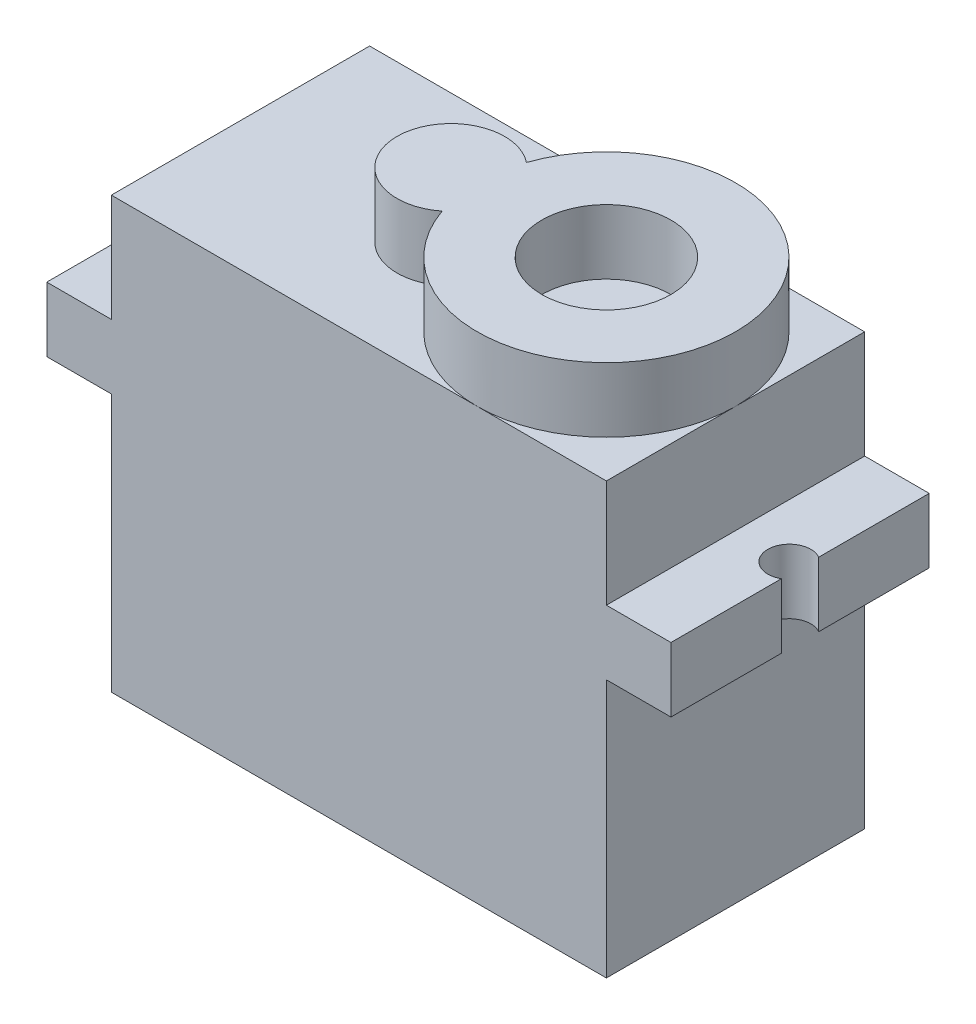
SolidWorks part; units mm, degrees
ref_plane "Front Plane" through (0, 0, 0) normal (0, 0, 1) x (1, 0, 0)
ref_plane "Top Plane" through (0, 0, 0) normal (0, 1, 0) x (1, 0, 0)
ref_plane "Right Plane" through (0, 0, 0) normal (1, 0, 0) x (0, 0, -1)
sketch "Sketch1" plane through (0, 0, 0) normal (0, 0, 1) x (1, 0, 0)
  line L0 (0, 0) -> (0, 9863.6126) construction
  line L1 (0, 0) -> (-9863.6126, 0) construction
  line L3 (-11.5, 0) -> (11.5, 0)
  line L4 (-11.5, 0) -> (-11.5, -12)
  line L5 (-11.5, -12) -> (11.5, -12)
  line L6 (11.5, 0) -> (11.5, -12)
  line L7 (-14.5, 0) -> (14.5, 0)
  line L8 (-14.5, 0) -> (-14.5, 3)
  line L9 (-14.5, 3) -> (14.5, 3)
  line L10 (14.5, 0) -> (14.5, 3)
  line L11 (-11.5, 3) -> (11.5, 3)
  line L12 (-11.5, 3) -> (-11.5, 8)
  line L13 (-11.5, 8) -> (11.5, 8)
  line L14 (11.5, 3) -> (11.5, 8)
  dimension "D1" = 23
  dimension "D2" = 29
  dimension "D3" = 3
  dimension "D4" = 12
  dimension "D5" = 5
  dimension "D6" = 23
extrude "Boss-Extrude1" add sketch "Sketch1" along normal mid plane 12 contours L6 L3 L4 L5 | L7 L10 L9 L8 L3 | L9 L14 L13 L12 region at (0, 1.5, 0) region at (0, -6, 0) region at (0, 5.5, 0)
sketch "Sketch2" plane through (0, 3, 0) normal (0, 1, 0) x (1, 0, 0)
  line L0 (11.5, -6) -> (11.5, 6) construction
  circle A0 centre (14, 0) radius 1
  circle A1 centre (-14, 0) radius 1
  dimension "D1" = 2
  dimension "D2" = 2.5
extrude "Cut-Extrude1" cut sketch "Sketch2" against normal through all
sketch "Sketch3" plane through (0, -12, 0) normal (0, -1, 0) x (1, 0, 0)
  line L0 (-11.5, -6) -> (11.5, -6) construction
  line L1 (11.5, 6) -> (11.5, -6) construction
  line L2 (0, 0) -> (0, 50000) construction
  line L3 (0, 0) -> (-50000, 0) construction
  circle A0 centre (9.5, -4) radius 1.25
  circle A1 centre (9.5, 4) radius 1.25
  circle A2 centre (-9.5, -4) radius 1.25
  circle A3 centre (-9.5, 4) radius 1.25
  circle A4 centre (9.5, -4) radius 1
  circle A5 centre (9.5, 4) radius 1
  circle A6 centre (-9.5, -4) radius 1
  circle A7 centre (-9.5, 4) radius 1
  dimension "D1" = 2.5
  dimension "D4" = 2
  dimension "D2" = 2
  dimension "D3" = 2
extrude "Cut-Extrude2" cut sketch "Sketch3" against normal blind 0.5
extrude "Cut-Extrude3" cut sketch "Sketch3<2>" against normal blind 12 contours A6 | A7 | A5 | A4 region at (9.5, -12, -4) region at (9.5, -12, 4) region at (-9.5, -12, -4) region at (-9.5, -12, 4)
sketch "Sketch3<2>" plane through (0, -12, 0) normal (0, -1, 0) x (1, 0, 0) same geometry as "Sketch3"
sketch "Sketch4" plane through (0, 8, 0) normal (0, 1, 0) x (1, 0, 0)
  arc A0 (-0.1717, -1.9576) -> (-0.1717, 1.9576) centre (5.5, 0) ccw
  arc A1 (-0.1717, 1.9576) -> (-0.1717, -1.9576) centre (-1.7265, 0) ccw
  circle A2 centre (5.5, 0) radius 3
  dimension "D1" = 12
  dimension "D2" = 5
  dimension "D3" = 6
extrude "Boss-Extrude2" add sketch "Sketch4" along normal blind 3
